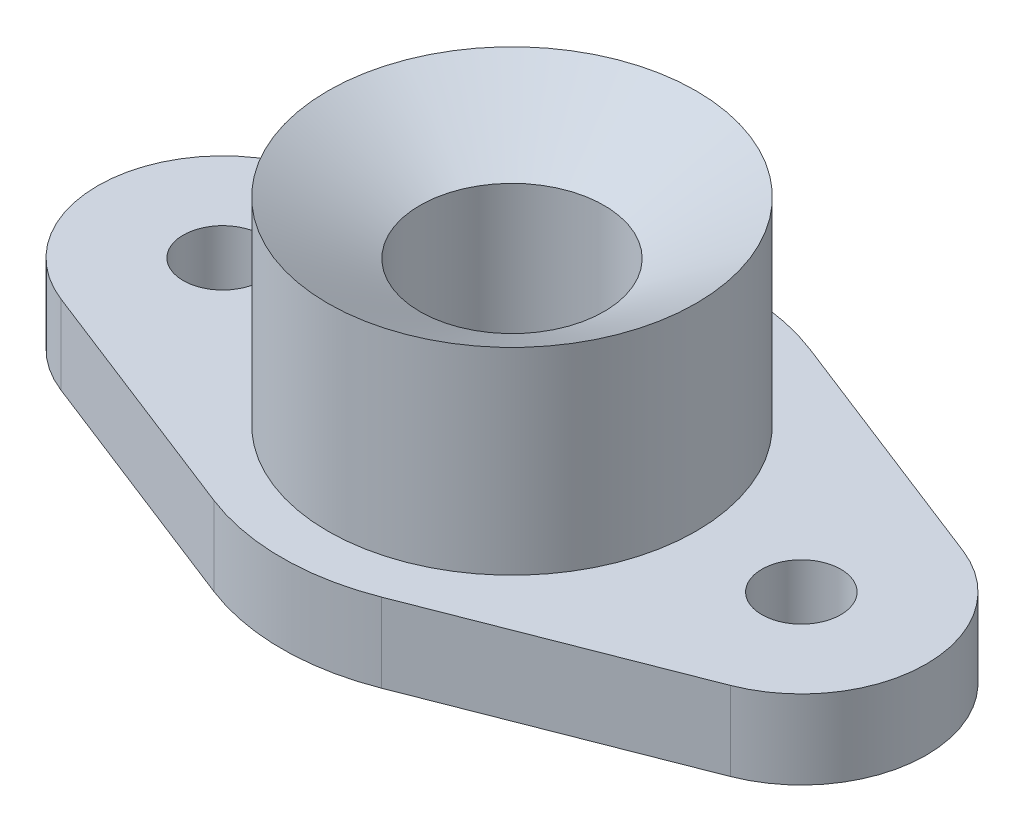
SolidWorks part; units mm, degrees
ref_plane "Front Plane" through (0, 0, 0) normal (0, 0, 1) x (1, 0, 0)
ref_plane "Top Plane" through (0, 0, 0) normal (0, 1, 0) x (1, 0, 0)
ref_plane "Right Plane" through (0, 0, 0) normal (1, 0, 0) x (0, 0, -1)
sketch "Sketch1" plane through (0, 0, 0) normal (0, 1, 0) x (1, 0, 0)
  line L0 (0, 0) -> (0, -80156.2893) construction
  line L1 (0, 0) -> (80156.2893, 0) construction
  line L2 (12.7273, 32.6039) -> (50.9091, 17.6993)
  line L3 (12.7273, -32.6039) -> (50.9091, -17.6993)
  line L4 (-12.7273, -32.6039) -> (-50.9091, -17.6993)
  line L5 (-12.7273, 32.6039) -> (-50.9091, 17.6993)
  arc A0 (-12.7273, -32.6039) -> (12.7273, -32.6039) centre (0, 0) ccw
  arc A1 (50.9091, -17.6993) -> (50.9091, 17.6993) centre (44, 0) ccw
  circle A2 centre (44, 0) radius 6
  circle A3 centre (-44, 0) radius 6
  arc A4 (-50.9091, -17.6993) -> (-50.9091, 17.6993) centre (-44, 0) cw
  circle A5 centre (0, 0) radius 28
  arc A6 (12.7273, 32.6039) -> (-12.7273, 32.6039) centre (0, 0) ccw
  dimension "D1" = 70
  dimension "D3" = 38
  dimension "D4" = 12
  dimension "D5" = 56
  dimension "D2" = 88
extrude "Boss-Extrude1" add sketch "Sketch1" along normal blind 42 contours A5 region at (0, 0, 0)
extrude "Boss-Extrude2" add sketch "Sketch1<3>" along normal blind 12
sketch "Sketch1<3>" plane through (0, 0, 0) normal (0, 1, 0) x (1, 0, 0) same geometry as "Sketch1"
hole_wizard "CSK for M2 Flat Head Machine Screw1" positions "Sketch2" profile "Sketch3" countersink size "M2" standard "ANSI Metric" end condition up to next
sketch "Sketch2" plane through (0, 42, 0) normal (0, 1, 0) x (1, 0, 0)
  point P0 (0, 0)
sketch "Sketch3" plane through (0, 42, 0) normal (1, 0, 0) x (0, 0, 1)
  line L0 (0, 0) -> (0, 42)
  line L1 (0, 42) -> (14, 42)
  line L2 (14, 42) -> (14, 8.0829)
  line L3 (14, 8.0829) -> (28, 0)
  line L5 (28, 0) -> (0, 0)
  line L6 (-14, 8.0829) -> (-28, 0) construction
  line L11 (0, -6.35) -> (0, 107.95) construction
  dimension "Thru Hole Dia." = 28
  dimension "Thru Hole Depth" = 42
  dimension "Near C'Sink Dia." = 56
  dimension "Near C'Sink Angle" = 120
